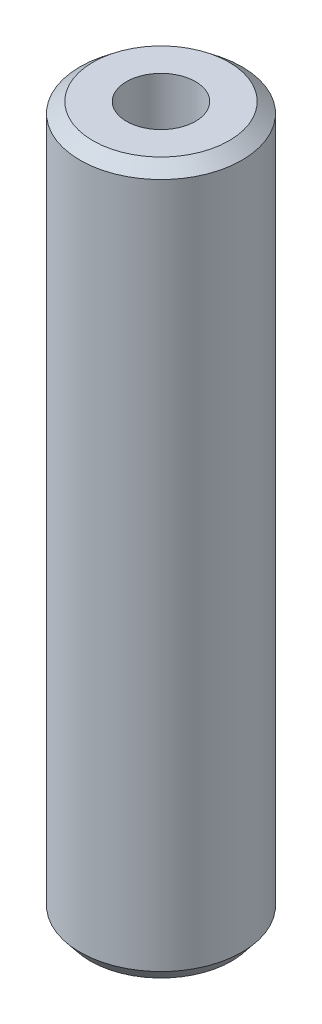
SolidWorks part; units mm, degrees
ref_plane "Front Plane" through (0, 0, 0) normal (0, 0, 1) x (1, 0, 0)
ref_plane "Top Plane" through (0, 0, 0) normal (0, 1, 0) x (1, 0, 0)
ref_plane "Right Plane" through (0, 0, 0) normal (1, 0, 0) x (0, 0, -1)
sketch "Sketch1" plane through (0, 0, 0) normal (0, 1, 0) x (1, 0, 0)
  circle A0 centre (0, 0) radius 27.5
  dimension "SHAFT_OD" = 55
extrude "Boss-Extrude1" add sketch "Sketch1" along normal blind 240.8209
sketch "Sketch2" plane through (0, 0, 0) normal (0, 1, 0) x (1, 0, 0)
  circle A0 centre (0, 0) radius 11.7069
  dimension "BORE_D" = 23.4137
extrude "Cut-Extrude1" cut sketch "Sketch2" along normal through all
chamfer "Chamfer1" distance 3.5264 angle 51.229 2 edges at (0, 240.8209, 27.5) (0, 0, 27.5) first distance on face at (0, 240.8209, 27.5) first distance on face at (0, 0, 11.7069)
